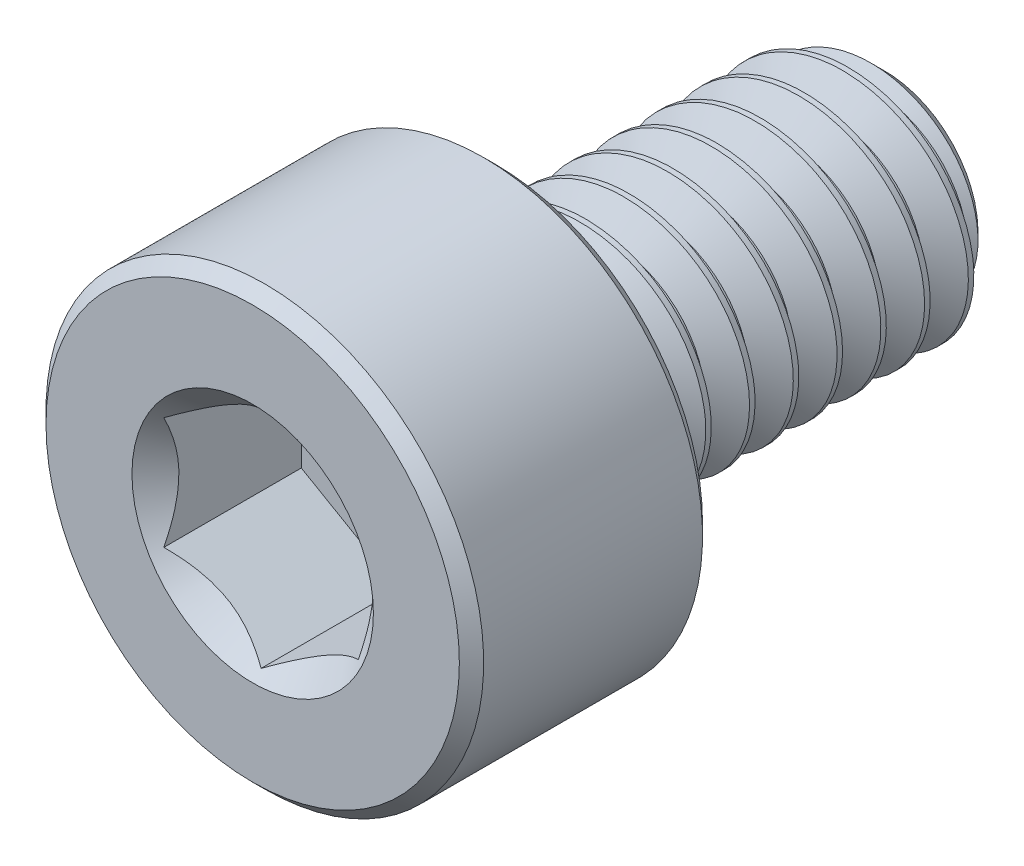
SolidWorks part; units mm, degrees
ref_plane "Front Plane" through (0, 0, 0) normal (0, 0, 1) x (1, 0, 0)
ref_plane "Top Plane" through (0, 0, 0) normal (0, 1, 0) x (1, 0, 0)
ref_plane "Right Plane" through (0, 0, 0) normal (1, 0, 0) x (0, 0, -1)
sketch "Sketch1" plane through (0, 0, 0) normal (1, 0, 0) x (0, 0, -1)
  line L0 (-3.25, 0) -> (3.25, 0) construction
  line L1 (3.25, 0) -> (3.25, 0.9577) construction
  line L2 (3.25, 0.9577) -> (2.9577, 1.25) construction
  line L3 (2.9577, 1.25) -> (2.9125, 1.25) construction
  line L4 (2.9125, 1.25) -> (-0.75, 1.25) construction
  line L5 (-0.75, 1.25) -> (-0.75, 2.25) construction
  line L6 (-0.75, 2.25) -> (-3.25, 2.25) construction
  line L7 (-3.25, 2.25) -> (-3.25, 0) construction
  line L8 (3.25, 0.9577) -> (3.25, 1.25) construction
  line L9 (3.2219, 1.2987) -> (3.4469, 0.909) construction
  line L10 (3.4469, 0.909) -> (3.6719, 1.2987) construction
  line L11 (3.6719, 1.2987) -> (3.2219, 1.2987) construction
  line L12 (3.4469, 1.2987) -> (3.4469, 1.25) construction
  line L13 (3.4469, 0.909) -> (3.4469, 0.9577) construction
  line L14 (3.4187, 0.9577) -> (3.475, 0.9577) construction
  line L15 (3.25, 1.25) -> (3.6437, 1.25) construction
  line L16 (3.2359, 1.2744) -> (3.6578, 1.2744) construction
  line L17 (3.25, 0) -> (3.25, -1.25) construction
  line L18 (-0.875, 2.25) -> (-0.75, 2.125) construction
  line L19 (-3.125, 2.25) -> (-3.25, 2.125) construction
  line L20 (-0.75, 1.25) -> (-0.75, 0) construction
  line L21 (-0.75, 0.625) -> (0.5833, 0.625) construction
  line L22 (0.5833, 0.625) -> (1.9167, 0.625) construction
  line L23 (1.9167, 0.625) -> (3.25, 0.625) construction
  line L24 (0.5833, 0.625) -> (0.5833, 1.25) construction
  line L25 (0.5833, 1.25) -> (0.5833, 2.25) construction
  line L26 (1.9167, 0.625) -> (1.9167, 2.25) construction
  point P0 (-3.25, 1)
  point P3 (2.125, 1.25)
  point P4 (0, 0)
  point P18 (1.9167, 1.25)
  point P22 (3.4469, 0.9577)
  point P24 (2.9125, 1.25)
  point P25 (3.4469, 1.25)
  point P28 (3.4469, 1.2744)
  point P29 (2.125, -1.25)
  point P30 (0.5833, 1.25)
  point P31 (-2, 2.25)
  point P37 (-1.1875, 2.25)
  point P38 (-3.0625, 2.25)
  point P45 (0.5833, 0.625)
  point P46 (1.9167, 0.625)
  dimension "D2" = 0.0563
  dimension "D7" = 0.125
  dimension "D8" = 0.125
  dimension "D9" = 0.125
  dimension "D10" = 0.0625
  dimension "D11" = 0.3125
  dimension "Drive Size" = 2
  dimension "Head Diameter" = 4.5
  dimension "Head Height" = 2.5
  dimension "Thread Pitch" = 0.45
  dimension "Thread Dia" = 2.5
  dimension "Length" = 4
  dimension "D12" = 0.3375
  dimension "D4" = 1.125
  dimension "D3" = 45
sketch "Sketch2" plane through (0, 0, 0) normal (1, 0, 0) x (0, 0, -1)
  line L0 (-3.25, 0) -> (-3.25, 2.125)
  line L1 (-3.125, 2.25) -> (-0.875, 2.25)
  line L2 (-0.75, 2.125) -> (-0.75, 1.375)
  line L4 (2.9577, 1.25) -> (3.25, 0.9577)
  line L5 (3.25, 0.9577) -> (3.25, 0)
  line L6 (-0.75, 2.25) -> (-3.25, 2.25) construction
  line L7 (3.25, 0) -> (-3.25, 0)
  line L8 (-3.125, 2.25) -> (-3.25, 2.125) construction
  line L10 (-3.125, 2.25) -> (-3.25, 2.125)
  line L14 (-0.875, 2.25) -> (-0.75, 2.125) construction
  line L16 (-0.875, 2.25) -> (-0.75, 2.125)
  line L17 (-0.75, 1.25) -> (-0.75, 2.25) construction
  line L19 (-0.625, 1.25) -> (2.9577, 1.25)
  line L20 (2.9125, 1.25) -> (-0.75, 1.25) construction
  arc A1 (-0.75, 1.375) -> (-0.625, 1.25) centre (-0.625, 1.375) ccw
  dimension "D3" = 0.125
revolve "Revolve1" add sketch "Sketch2" angle 360 about L7
sketch "Sketch3" plane through (0, 0, 3.25) normal (0, 0, 1) x (1, 0, 0)
  line L1 (1, -0.5774) -> (1, 0.5774)
  line L2 (1, 0.5774) -> (0, 1.1547)
  line L3 (0, 1.1547) -> (-1, 0.5774)
  line L4 (-1, 0.5774) -> (-1, -0.5774)
  line L5 (-1, -0.5774) -> (0, -1.1547)
  line L6 (0, -1.1547) -> (1, -0.5774)
  circle A0 centre (0, 0) radius 1 construction
  circle A1 centre (0, 0) radius 2.25 construction
  circle A2 centre (0, 0) radius 2.25 construction
  circle A3 centre (0, 0) radius 1.1547 construction
  point P13 (0, 0)
  dimension "D1" = 2.3094
extrude "Cut-Extrude1" cut sketch "Sketch3" against normal offset from surface (1.5 mm away) 1 up to face at (0, 2.125, 0.75)
sketch "Sketch4" plane through (0, 0, 3.25) normal (0, 0, 1) x (1, 0, 0)
  circle A0 centre (0, 0) radius 1.2413
  dimension "D1" = 2.4826
extrude "Cut-Extrude2" cut sketch "Sketch4" against normal up to vertex (1.25 mm away) draft 45 up to point (0, 2.25, 2)
sketch "Sketch11" plane through (0, 0, 0) normal (1, 0, 0) x (0, 0, -1)
  line L0 (-3.25, 0) -> (3.25, 0) construction
  line L1 (-3.25, 0) -> (3.25, 0) construction
  line L2 (0, 0) -> (0, 1.25) construction
  line L3 (2.9125, 1.25) -> (-0.75, 1.25) construction
  line L4 (2.5, 0) -> (2.5, 1.25) construction
  line L6 (3.25, 0.9577) -> (3.25, 1.25) construction
  point P2 (0, 0)
  point P3 (2.5, 0)
  dimension "D1" = 0.75
  dimension "D2" = 0.75
sketch "Sketch6" plane through (0, 0, -3.25) normal (0, 0, -1) x (-1, 0, 0)
  circle A0 centre (0, 0) radius 1.25
curve "Helix/Spiral1" pitch 0.45 height 4.45 turns 9.8889
sketch "Sketch10" plane through (0, 0, 0) normal (1, 0, 0) x (0, 0, -1)
  line L0 (-0.625, -2.25) -> (-0.625, 2.25)
  line L5 (-3.25, 0) -> (3.25, 0) construction
  line L6 (-0.625, 1.25) -> (-0.625, -1.25) construction
  point P3 (-0.625, 0)
split "Split1" trim tools "Sketch10" bodies to split 106 resulting bodies 114 115
sketch "Sketch7" plane through (0, 0, 0) normal (1, 0, 0) x (0, 0, -1)
  line L0 (3.2359, 1.2744) -> (3.6578, 1.2744)
  line L1 (3.6578, 1.2744) -> (3.475, 0.9577)
  line L2 (3.475, 0.9577) -> (3.4187, 0.9577)
  line L3 (3.4187, 0.9577) -> (3.2359, 1.2744)
sweep "Cut-Sweep1" cut profiles "Sketch7" path "Helix/Spiral1" align with end faces yes
sketch "Sketch8" plane through (0, 0, 0) normal (1, 0, 0) x (0, 0, -1)
  line L0 (-0.75, 0) -> (-0.75, 1.25)
  line L1 (-0.625, -1.25) -> (-0.625, 1.25) construction
  line L2 (-0.75, 1.25) -> (-0.625, 1.25)
  line L4 (-0.625, 1.25) -> (0.0967, 0)
  line L5 (0.0967, 0) -> (-0.75, 0)
  line L6 (2.9125, 1.25) -> (-0.75, 1.25) construction
  line L7 (-3.25, 0) -> (3.25, 0) construction
  dimension "D1" = 60
revolve "Revolve2" add sketch "Sketch8" angle 360 about L5
equation "\"D2@Sketch1\" = \"Thread Pitch@Sketch1\" / 8"
equation "\"D4@Helix/Spiral1\" = \"Thread Pitch@Sketch1\""
equation "\"D7@Sketch1\" = \"Head Height@Sketch1\" * .05"
equation "\"D8@Sketch1\"=\"D7@Sketch1\""
equation "\"D9@Sketch1\"=\"D7@Sketch1\""
equation "\"D10@Sketch1\"=\"D7@Sketch1\"/2"
equation "\"D11@Sketch1\"=\"D10@Sketch1\"*5"
equation "\"D4@Sketch1\"=\"Thread Pitch@Sketch1\"*2.5"
equation "\"D12@Sketch1\"=\"Thread Pitch@Sketch1\"*.75"
equation "\"D3@Helix/Spiral1\"=\"Length@Sketch1\"+\"Thread Pitch@Sketch1\""
equation "\"D3@Sketch2\"=\"Thread Dia@Sketch1\"*0.05"
equation "\"D1@Sketch11\"=\"Length@Sketch1\"*0.1875"
equation "\"D2@Sketch11\"=\"D1@Sketch11\""
equation "\"D1@Sketch4\"=\"D1@Sketch3\"*1.075"
